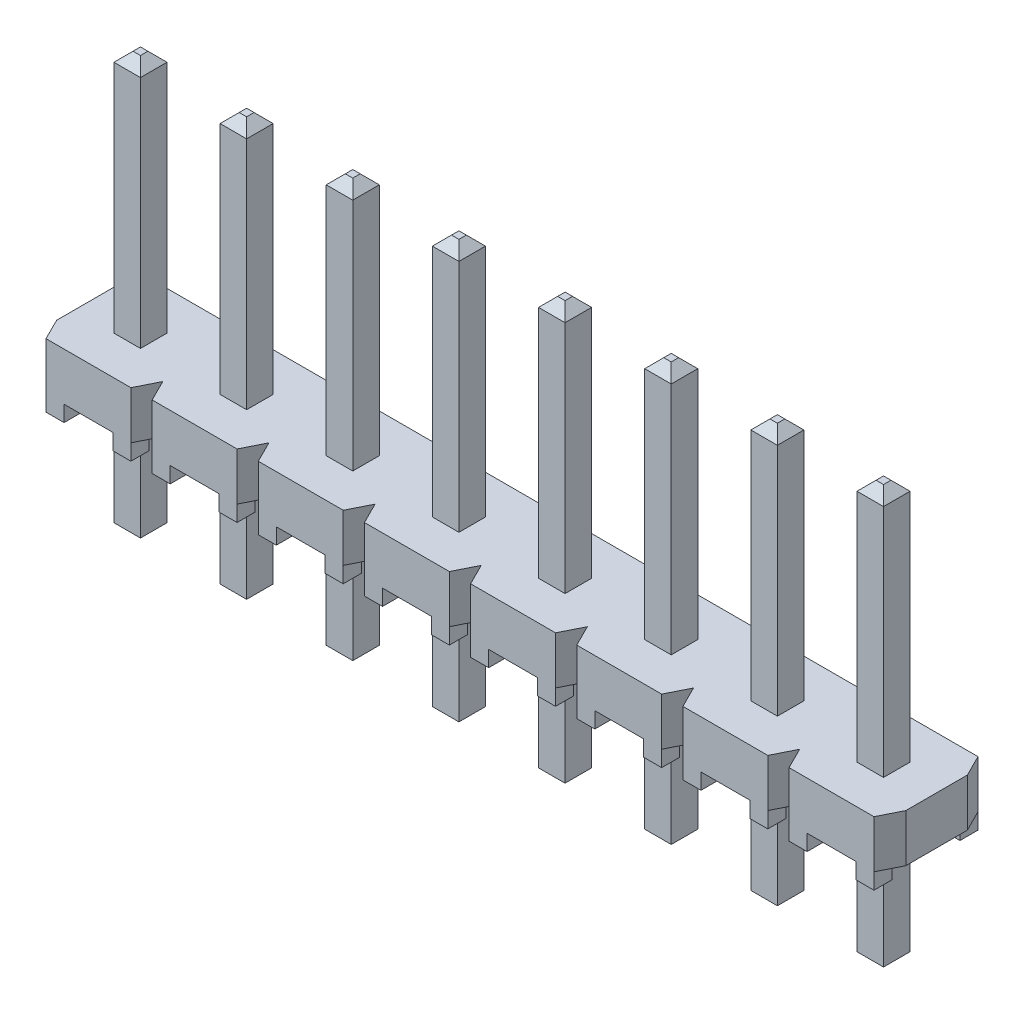
SolidWorks part; units mm, degrees
ref_plane "Front" through (0, 0, 0) normal (0, 0, 1) x (1, 0, 0)
ref_plane "Top" through (0, 0, 0) normal (0, 1, 0) x (1, 0, 0)
ref_plane "Side" through (0, 0, 0) normal (1, 0, 0) x (0, 0, -1)
sketch "Sketch1" plane through (0, 0, 0) normal (0, 1, 0) x (1, 0, 0)
  line L0 (10.16, -1.2446) -> (-10.16, 1.2446) construction
  line L1 (-10.16, 1.2446) -> (10.16, 1.2446)
  line L2 (-10.16, 1.2446) -> (-10.16, -1.2446)
  line L3 (-10.16, -1.2446) -> (10.16, -1.2446)
  line L4 (10.16, 1.2446) -> (10.16, -1.2446)
  dimension "D1" = 20.32
  dimension "D2" = 2.4892
extrude "Base-Extrude" add sketch "Sketch1" along normal mid plane 1.143
sketch "Sketch3" plane through (0, 0.5715, 0) normal (0, 1, 0) x (-1, 0, 0)
  line L0 (7.5339, 0) -> (10.4044, 0) construction
  line L1 (7.366, 1.2446) -> (7.874, 1.2446)
  line L2 (7.366, -1.2446) -> (7.874, -1.2446)
  line L3 (7.874, 1.2446) -> (7.62, 0.7366)
  line L4 (7.874, -1.2446) -> (7.62, -0.7366)
  line L5 (7.62, 0.7366) -> (7.366, 1.2446)
  line L6 (7.62, -0.7366) -> (7.366, -1.2446)
  line L7 (7.62, 1.2446) -> (7.62, 0.7366) construction
  line L8 (7.62, -1.2446) -> (7.62, -0.7366) construction
  line L9 (10.16, 1.2446) -> (-10.16, 1.2446) construction
  line L11 (8.89, -1.4521) -> (8.89, 2.3817) construction
  line L12 (10.16, -0.7366) -> (10.414, -1.2446)
  line L13 (10.16, 0.7366) -> (10.414, 1.2446)
  line L14 (9.906, -1.2446) -> (10.16, -0.7366)
  line L15 (9.906, 1.2446) -> (10.16, 0.7366)
  line L16 (10.414, -1.2446) -> (9.906, -1.2446)
  line L17 (10.414, 1.2446) -> (9.906, 1.2446)
  line L18 (10.16, -1.2446) -> (10.16, 1.2446) construction
  dimension "D1" = 0.508
  dimension "D2" = 0.508
  dimension "D3" = 1.27
  dimension "D4" = 1.27
extrude "Snap Grooves" cut sketch "Sketch3" against normal through all
sketch "Sketch4" plane through (0, -0.5715, 0) normal (0, -1, 0) x (1, 0, 0)
  line L0 (-8.89, 1.3819) -> (-8.89, -1.499) construction
  line L1 (-9.906, 1.2446) -> (-7.874, 1.2446) construction
  line L2 (-9.906, 1.2446) -> (-9.4742, 1.2446)
  line L3 (-9.906, 1.2446) -> (-9.906, 0.8128)
  line L4 (-9.906, 0.8128) -> (-9.4742, 0.8128)
  line L5 (-9.4742, 1.2446) -> (-9.4742, 0.8128)
  line L6 (-8.3058, 1.2446) -> (-8.3058, 0.8128)
  line L7 (-7.874, 0.8128) -> (-8.3058, 0.8128)
  line L8 (-7.874, 1.2446) -> (-7.874, 0.8128)
  line L9 (-7.874, 1.2446) -> (-8.3058, 1.2446)
  line L11 (-10.16, -0.7366) -> (-10.16, 0.7366) construction
  line L12 (-9.3213, 0) -> (-10.8923, 0) construction
  line L14 (-7.874, -1.2446) -> (-8.3058, -1.2446)
  line L15 (-7.874, -1.2446) -> (-7.874, -0.8128)
  line L16 (-7.874, -0.8128) -> (-8.3058, -0.8128)
  line L17 (-8.3058, -1.2446) -> (-8.3058, -0.8128)
  line L18 (-9.4742, -1.2446) -> (-9.4742, -0.8128)
  line L19 (-9.906, -0.8128) -> (-9.4742, -0.8128)
  line L20 (-9.906, -1.2446) -> (-9.906, -0.8128)
  line L21 (-9.906, -1.2446) -> (-9.4742, -1.2446)
  dimension "D1" = 0.4318
  dimension "D2" = 0.4318
  dimension "D3" = 1.27
extrude "Standoffs" add sketch "Sketch4" along normal blind 0.381
pattern_linear "Position Pattern" count 8 spacing 2.54 along (1, 0, 0) of "Snap Grooves", "Standoffs"
ref_plane "Position 1 Plane" through (-8.89, 0, 0) normal (-1, 0, 0) x (0, 0, 1)
sketch "Sketch5" plane through (-8.89, 0, 0) normal (-1, 0, 0) x (0, 0, 1)
  line L0 (0, 6.4135) -> (0, -3.5865) construction
  line L1 (-0.3175, 6.4135) -> (0.3175, 6.4135)
  line L2 (-0.3175, 6.4135) -> (-0.3175, -3.5865)
  line L3 (-0.3175, -3.5865) -> (0.3175, -3.5865)
  line L4 (0.3175, 6.4135) -> (0.3175, -3.5865)
  line L5 (1.2446, -0.5715) -> (1.2446, 0.5715) construction
  line L6 (-0.7366, 0.5715) -> (0.7366, 0.5715) construction
  dimension "D1" = 1.2446
  dimension "D2" = 0.635
  dimension "D3" = 5.842
  dimension "D4" = 10
extrude "Terminal -TH" add sketch "Sketch5" along normal mid plane 0.635
chamfer "T1 Tip1" distance 0.2286 angle 45 8 edges at (-8.5725, 6.4135, 0) (-8.89, 6.4135, -0.3175) (-9.2075, 6.4135, 0) (-8.89, 6.4135, 0.3175) (-8.89, -3.5865, -0.3175) (-9.2075, -3.5865, 0) (-8.89, -3.5865, 0.3175) (-8.5725, -3.5865, 0)
pattern_linear "Terminal Pattern" count 1 spacing 2.54 along (0, 0, -1) count 8 spacing 2.54 along (1, 0, 0) of "Terminal -TH", "T1 Tip1"
ref_plane "Initial -S Polarize Plane" through (11.43, 0, 0) normal (1, 0, 0) x (0, 0, -1)
ref_plane "-S Polarize Plane" through (8.89, 0, 0) normal (1, 0, 0) x (0, 0, -1)
ref_plane "Initial -D Polarize Plane" through (-11.43, 0, 0) normal (-1, 0, 0) x (0, 0, 1)
ref_plane "-D Polarize Plane" through (-10.16, 0, 0) normal (-1, 0, 0) x (0, 0, 1)
